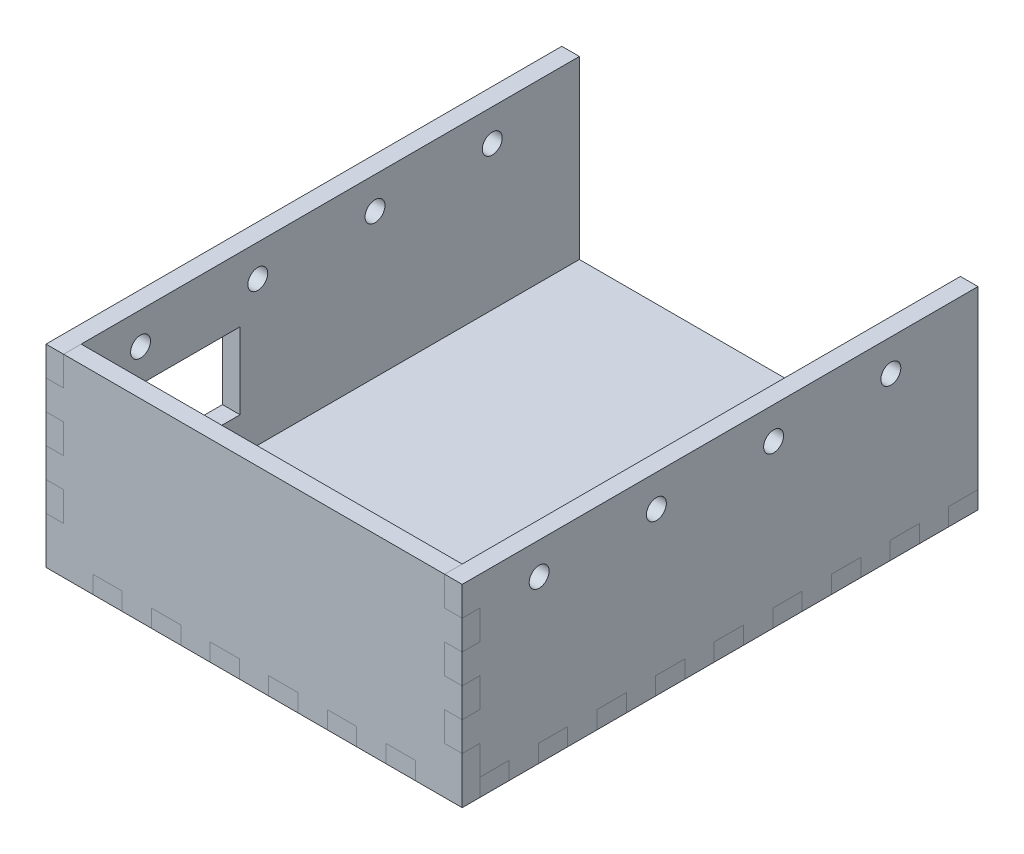
SolidWorks part; units mm, degrees
ref_plane "Front Plane" through (0, 0, 0) normal (0, 0, 1) x (1, 0, 0)
ref_plane "Top Plane" through (0, 0, 0) normal (0, 1, 0) x (1, 0, 0)
ref_plane "Right Plane" through (0, 0, 0) normal (1, 0, 0) x (0, 0, -1)
sketch "Sketch1" plane through (0, 0, 0) normal (0, 1, 0) x (1, 0, 0)
  line L36 (65, -5) -> (68, -5)
  line L37 (68, -5) -> (68, -10)
  line L38 (68, -10) -> (65, -10)
  line L39 (65, -10) -> (65, -15)
  line L40 (65, -15) -> (68, -15)
  line L41 (68, -15) -> (68, -20)
  line L42 (68, -20) -> (65, -20)
  line L43 (65, -20) -> (65, -25)
  line L44 (65, -25) -> (68, -25)
  line L45 (68, -25) -> (68, -30)
  line L46 (68, -30) -> (65, -30)
  line L47 (65, -30) -> (65, -35)
  line L48 (65, -35) -> (68, -35)
  line L49 (68, -35) -> (68, -40)
  line L50 (68, -40) -> (65, -40)
  line L51 (65, -40) -> (65, -45)
  line L52 (65, -45) -> (68, -45)
  line L53 (68, -45) -> (68, -50)
  line L54 (68, -50) -> (65, -50)
  line L55 (65, -50) -> (65, -55)
  line L56 (65, -55) -> (68, -55)
  line L57 (68, -55) -> (68, -60)
  line L58 (68, -60) -> (65, -60)
  line L59 (65, -60) -> (65, -65)
  line L60 (65, -65) -> (68, -65)
  line L61 (68, -65) -> (68, -70)
  line L62 (68, -70) -> (65, -70)
  line L63 (65, -70) -> (65, -75)
  line L64 (65, -75) -> (68, -75)
  line L65 (68, -75) -> (68, -80)
  line L66 (68, -80) -> (65, -80)
  line L67 (65, -80) -> (65, -85)
  line L68 (65, -85) -> (68, -85)
  line L69 (68, -85) -> (68, -90)
  line L70 (68, -90) -> (65, -90)
  line L72 (65, -90) -> (60, -90)
  line L73 (60, -90) -> (60, -93)
  line L74 (60, -93) -> (55, -93)
  line L75 (55, -93) -> (55, -90)
  line L76 (55, -90) -> (50, -90)
  line L77 (50, -90) -> (50, -93)
  line L78 (50, -93) -> (45, -93)
  line L79 (45, -93) -> (45, -90)
  line L80 (45, -90) -> (40, -90)
  line L81 (40, -90) -> (40, -93)
  line L82 (40, -93) -> (35, -93)
  line L83 (35, -93) -> (35, -90)
  line L84 (35, -90) -> (30, -90)
  line L85 (30, -90) -> (30, -93)
  line L86 (30, -93) -> (25, -93)
  line L87 (25, -93) -> (25, -90)
  line L88 (25, -90) -> (20, -90)
  line L89 (20, -90) -> (20, -93)
  line L90 (20, -93) -> (15, -93)
  line L91 (15, -93) -> (15, -90)
  line L92 (15, -90) -> (10, -90)
  line L93 (10, -90) -> (10, -93)
  line L94 (10, -93) -> (5, -93)
  line L95 (5, -93) -> (5, -90)
  line L96 (5, -90) -> (0, -90)
  line L98 (0, -90) -> (-3, -90)
  line L99 (-3, -90) -> (-3, -85)
  line L100 (-3, -85) -> (0, -85)
  line L101 (0, -85) -> (0, -80)
  line L102 (0, -80) -> (-3, -80)
  line L103 (-3, -80) -> (-3, -75)
  line L104 (-3, -75) -> (0, -75)
  line L105 (0, -75) -> (0, -70)
  line L106 (0, -70) -> (-3, -70)
  line L107 (-3, -70) -> (-3, -65)
  line L108 (-3, -65) -> (0, -65)
  line L109 (0, -65) -> (0, -60)
  line L110 (0, -60) -> (-3, -60)
  line L111 (-3, -60) -> (-3, -55)
  line L112 (-3, -55) -> (0, -55)
  line L113 (0, -55) -> (0, -50)
  line L114 (0, -50) -> (-3, -50)
  line L115 (-3, -50) -> (-3, -45)
  line L116 (-3, -45) -> (0, -45)
  line L117 (0, -45) -> (0, -40)
  line L118 (0, -40) -> (-3, -40)
  line L119 (-3, -40) -> (-3, -35)
  line L120 (-3, -35) -> (0, -35)
  line L121 (0, -35) -> (0, -30)
  line L122 (0, -30) -> (-3, -30)
  line L123 (-3, -30) -> (-3, -25)
  line L124 (-3, -25) -> (0, -25)
  line L125 (0, -25) -> (0, -20)
  line L126 (0, -20) -> (-3, -20)
  line L127 (-3, -20) -> (-3, -15)
  line L128 (-3, -15) -> (0, -15)
  line L129 (0, -15) -> (0, -10)
  line L130 (0, -10) -> (-3, -10)
  line L131 (-3, -10) -> (-3, -5)
  line L132 (-3, -5) -> (65, -5)
  dimension "D4" = 9
extrude "Boss-Extrude1" add sketch "Sketch1" along normal blind 3
ref_plane "Plane1" through (32.5, 0, 0) normal (-1, 0, 0) x (0, 0, 1)
sketch "Sketch3" plane through (0, 0, 0) normal (-1, 0, 0) x (0, 0, 1)
  line L0 (10, 0) -> (15, 0)
  line L4 (10, 3) -> (10, 0)
  line L5 (10, 3) -> (10, 0) construction
  line L6 (15, 0) -> (15, 3)
  line L7 (15, 3) -> (20, 3)
  line L8 (20, 3) -> (20, 0)
  line L9 (20, 0) -> (25, 0)
  line L10 (25, 0) -> (25, 3)
  line L11 (25, 3) -> (30, 3)
  line L12 (30, 3) -> (30, 0)
  line L13 (30, 0) -> (35, 0)
  line L14 (35, 0) -> (35, 3)
  line L15 (35, 3) -> (40, 3)
  line L16 (40, 3) -> (40, 0)
  line L17 (40, 0) -> (45, 0)
  line L18 (45, 0) -> (45, 3)
  line L19 (45, 3) -> (50, 3)
  line L20 (50, 3) -> (50, 0)
  line L21 (50, 0) -> (55, 0)
  line L22 (55, 0) -> (55, 3)
  line L23 (55, 3) -> (60, 3)
  line L24 (60, 3) -> (60, 0)
  line L25 (60, 0) -> (65, 0)
  line L26 (65, 0) -> (65, 3)
  line L27 (65, 3) -> (70, 3)
  line L28 (70, 3) -> (70, 0)
  line L29 (70, 0) -> (75, 0)
  line L30 (75, 0) -> (75, 3)
  line L31 (75, 3) -> (80, 3)
  line L32 (80, 3) -> (80, 0)
  line L33 (80, 0) -> (85, 0)
  line L34 (85, 0) -> (85, 3)
  line L35 (85, 3) -> (90, 3)
  line L76 (93, 28) -> (93, 33)
  line L77 (90, 28) -> (93, 28)
  line L78 (90, 23) -> (90, 28)
  line L79 (93, 23) -> (90, 23)
  line L80 (93, 18) -> (93, 23)
  line L81 (90, 18) -> (93, 18)
  line L82 (90, 13) -> (90, 18)
  line L83 (93, 13) -> (90, 13)
  line L84 (93, 8) -> (93, 13)
  line L85 (90, 8) -> (93, 8)
  line L86 (90, 3) -> (90, 8)
  line L89 (10, 3) -> (5, 3)
  line L90 (5, 33) -> (5, 3)
  line L92 (90, 3) -> (90, 0) [skipped]
  line L103 (93, 33) -> (5, 33)
  point P7 (61.7348, 24.8696)
  dimension "D1" = 9
extrude "Boss-Extrude2" add sketch "Sketch3" along normal blind 3 separate body
mirror "Mirror1" about plane through (32.5, 0, 0) normal (-1, 0, 0) of bodies 102
sketch "Sketch5" plane through (0, 0, 90) normal (0, 0, 1) x (1, 0, 0)
  line L0 (60, 0) -> (68, 0)
  line L1 (15, 0) -> (15, 3)
  line L2 (68, 8) -> (65, 8)
  line L3 (65, 8) -> (65, 13)
  line L4 (65, 13) -> (68, 13)
  line L5 (68, 13) -> (68, 18)
  line L6 (68, 18) -> (65, 18)
  line L7 (65, 18) -> (65, 23)
  line L8 (65, 23) -> (68, 23)
  line L9 (68, 23) -> (68, 28)
  line L10 (68, 28) -> (65, 28)
  line L11 (65, 28) -> (65, 33)
  line L12 (65, 33) -> (0, 33)
  line L13 (0, 33) -> (0, 28)
  line L14 (0, 28) -> (-3, 28)
  line L15 (-3, 28) -> (-3, 23)
  line L16 (-3, 23) -> (0, 23)
  line L17 (0, 23) -> (0, 18)
  line L18 (0, 18) -> (-3, 18)
  line L19 (-3, 18) -> (-3, 13)
  line L20 (-3, 13) -> (0, 13)
  line L21 (0, 13) -> (0, 8)
  line L22 (0, 8) -> (-3, 8)
  line L23 (-3, 8) -> (-3, 3)
  line L24 (-3, 3) -> (-3, 0)
  line L25 (-3, 0) -> (0, 0)
  line L26 (5, 0) -> (5, 3)
  line L27 (5, 3) -> (10, 3)
  line L28 (10, 3) -> (10, 0)
  line L29 (0, 0) -> (5, 0)
  line L30 (15, 3) -> (20, 3)
  line L31 (20, 3) -> (20, 0)
  line L32 (10, 0) -> (15, 0)
  line L33 (25, 0) -> (25, 3)
  line L34 (25, 3) -> (30, 3)
  line L35 (30, 3) -> (30, 0)
  line L36 (20, 0) -> (25, 0)
  line L37 (35, 0) -> (35, 3)
  line L38 (35, 3) -> (40, 3)
  line L39 (40, 3) -> (40, 0)
  line L40 (30, 0) -> (35, 0)
  line L41 (45, 0) -> (45, 3)
  line L42 (45, 3) -> (50, 3)
  line L43 (50, 3) -> (50, 0)
  line L44 (40, 0) -> (45, 0)
  line L45 (55, 0) -> (55, 3)
  line L46 (55, 3) -> (60, 3)
  line L47 (60, 3) -> (60, 0)
  line L48 (50, 0) -> (55, 0)
  line L50 (68, 0) -> (68, 8)
  line L53 (65, 0) -> (65, 3) [skipped]
  line L54 (65, 3) -> (70, 3) [skipped]
  line L55 (70, 3) -> (70, 0) [skipped]
  line L56 (60, 0) -> (65, 0) [skipped]
  dimension "D1" = 7
extrude "Boss-Extrude3" add sketch "Sketch5" along normal blind 3 separate body
sketch "Sketch6" plane through (-3, 0, 0) normal (-1, 0, 0) x (0, 0, 1)
  circle A0 centre (19.8677, 27.5648) radius 1.7
  circle A3 centre (39.8677, 27.5648) radius 1.7
  circle A4 centre (59.8677, 27.5648) radius 1.7
  circle A5 centre (79.8677, 27.5648) radius 1.7
  point P3 (0, 0)
  dimension "D1" = 4
extrude "Cut-Extrude1" cut sketch "Sketch6" against normal blind 76
sketch "Sketch7" plane through (-3, 0, 0) normal (-1, 0, 0) x (0, 0, 1)
  line L1 (62.8955, 9.0058) -> (83.8955, 9.0058)
  line L2 (62.8955, 9.0058) -> (62.8955, 22.0058)
  line L3 (62.8955, 22.0058) -> (83.8955, 22.0058)
  line L4 (83.8955, 9.0058) -> (83.8955, 22.0058)
  point P4 (62.8955, 9.0058)
  dimension "D1" = 21
  dimension "D2" = 13
extrude "Cut-Extrude2" cut sketch "Sketch7" against normal blind 6
equation "\"hardboard_thickness\"=3"
equation "\"D1@Boss-Extrude1\"=\"hardboard_thickness\""
equation "\"D1@Boss-Extrude3\"=\"hardboard_thickness\""
